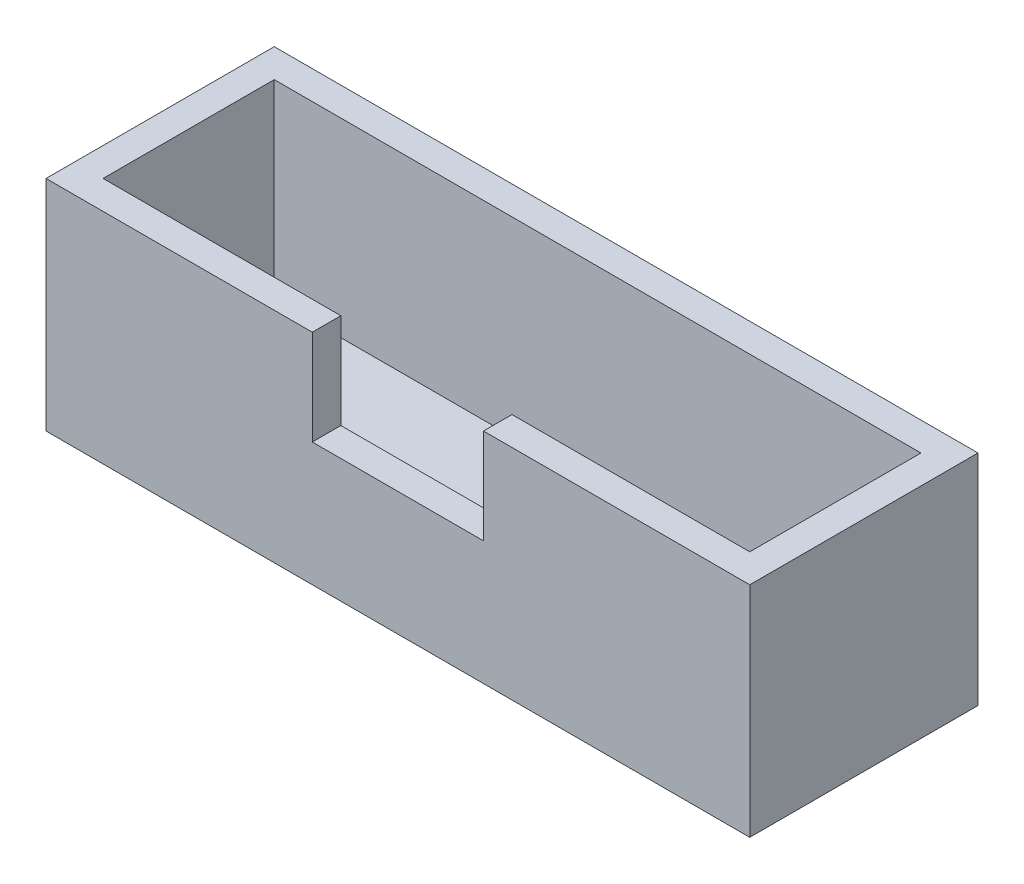
SolidWorks part; units mm, degrees
ref_plane "Front Plane" through (0, 0, 0) normal (0, 0, 1) x (1, 0, 0)
ref_plane "Top Plane" through (0, 0, 0) normal (0, 1, 0) x (1, 0, 0)
ref_plane "Right Plane" through (0, 0, 0) normal (1, 0, 0) x (0, 0, -1)
sketch "Sketch1" plane through (0, 0, 0) normal (0, 1, 0) x (1, 0, 0)
  line L1 (-19.0877, -3.3368) -> (48.9123, -3.3368)
  line L2 (-19.0877, -3.3368) -> (-19.0877, -21.3368)
  line L3 (-19.0877, -21.3368) -> (48.9123, -21.3368)
  line L4 (48.9123, -3.3368) -> (48.9123, -21.3368)
  line L5 (-22.0877, -0.3368) -> (51.9123, -0.3368)
  line L6 (-22.0877, -0.3368) -> (-22.0877, -24.3368)
  line L7 (-22.0877, -24.3368) -> (51.9123, -24.3368)
  line L8 (51.9123, -0.3368) -> (51.9123, -24.3368)
  dimension "D1" = 68
  dimension "D2" = 18
  dimension "D3" = 3
  dimension "D4" = 3
  dimension "D5" = 3
  dimension "D6" = 3
extrude "Boss-Extrude1" add sketch "Sketch1" along normal blind 20
extrude "Boss-Extrude2" add sketch "Sketch1<3>" against normal blind 3 contours L4 L1 L2 L3 | L8 L5 L6 L7 L1 L4 L3 L2 region at (14.9123, 0, 12.3368) region at (14.9123, 0, 1.1148)
sketch "Sketch1<3>" plane through (0, 0, 0) normal (0, 1, 0) x (1, 0, 0) same geometry as "Sketch1"
sketch "Sketch4" plane through (0, 0, 21.3368) normal (0, 0, -1) x (-1, 0, 0)
  line L0 (19.0877, 20) -> (19.0877, 0) construction
  line L1 (-5.9123, 20) -> (-23.9123, 20)
  line L2 (-5.9123, 20) -> (-5.9123, 10)
  line L3 (-5.9123, 10) -> (-23.9123, 10)
  line L4 (-23.9123, 20) -> (-23.9123, 10)
  line L5 (-48.9123, 20) -> (-48.9123, 0) construction
  line L6 (19.0877, 20) -> (-48.9123, 20) construction
  line L7 (19.0877, 0) -> (-48.9123, 0) construction
  dimension "D1" = 25
  dimension "D2" = 25
  dimension "D3" = 0
  dimension "D4" = 10
extrude "Cut-Extrude1" cut sketch "Sketch4" against normal up to next
equation "\"camera thickness\"= 18"
equation "\"camera height\"= 40"
equation "\"camera width\"= 68"
equation "\"side to camera\"= 25"
equation "\"D1@Sketch1\"=\"camera width\""
equation "\"D2@Sketch1\"=\"camera thickness\""
equation "\"mount thickness\"=3"
equation "\"D3@Sketch1\"=\"mount thickness\""
equation "\"D4@Sketch1\"=\"mount thickness\""
equation "\"D5@Sketch1\"=\"mount thickness\""
equation "\"D6@Sketch1\"=\"mount thickness\""
equation "\"D1@Boss-Extrude1\"=\"camera height\"/2"
equation "\"D1@Boss-Extrude2\"=\"mount thickness\""
equation "\"D1@Sketch4\"=\"side to camera\""
equation "\"D2@Sketch4\"=\"side to camera\""
equation "\"D4@Sketch4\"=\"camera height\"/4"
equation "\"light thickness\"= 14.1"
equation "\"light inner diameter\"= 66"
